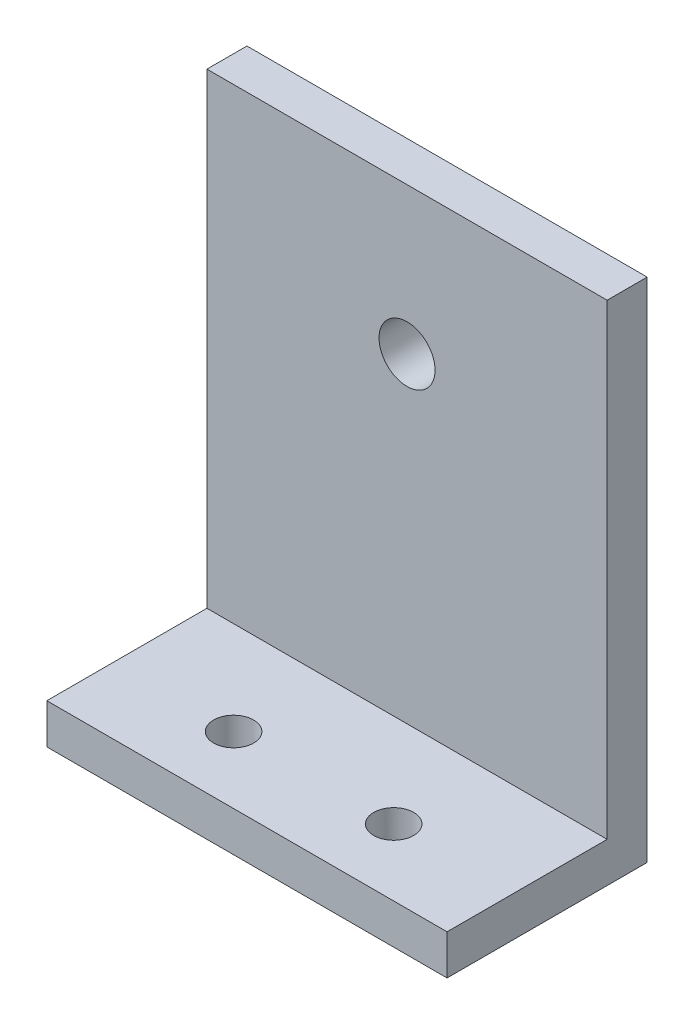
SolidWorks part; units mm, degrees
material "6063-O"
ref_plane "Front" through (0, 0, 0) normal (0, 0, 1) x (1, 0, 0)
ref_plane "Top" through (0, 0, 0) normal (0, 1, 0) x (1, 0, 0)
ref_plane "Right" through (0, 0, 0) normal (1, 0, 0) x (0, 0, -1)
sketch "草图1" plane through (0, 0, 0) normal (1, 0, 0) x (0, 0, -1)
  line L0 (0, 0) -> (0, 35)
  line L1 (0, 35) -> (3, 35)
  line L2 (3, 35) -> (3, -3)
  line L3 (0, 0) -> (-35, 0)
  line L4 (-35, 0) -> (-35, -3)
  line L5 (-35, -3) -> (3, -3)
  dimension "D1" = 35
  dimension "D2" = 3
  dimension "D3" = 38
  dimension "D4" = 35
extrude "凸台-拉伸1" add sketch "草图1" along normal blind 30
sketch "草图2" plane through (0, 0, 0) normal (0, 1, 0) x (1, 0, 0)
  line L0 (15, 0) -> (15, -35) construction
  line L1 (30, 0) -> (0, 0) construction
  line L2 (30, -35) -> (0, -35) construction
  line L3 (30, 3) -> (0, 3) construction
  line L4 (0, -35) -> (0, -25)
  line L5 (0, 0) -> (0, -35) construction
  line L6 (0, -25) -> (30, -25)
  line L7 (30, 0) -> (30, -35) construction
  line L8 (30, -25) -> (30, -35)
  line L9 (30, -35) -> (0, -35)
  circle A0 centre (9, -7) radius 1.5
  circle A1 centre (9, -19) radius 1.5
  circle A2 centre (21, -19) radius 1.5
  circle A3 centre (21, -7) radius 1.5
  dimension "D1" = 3
  dimension "D2" = 3
  dimension "D3" = 6
  dimension "D4" = 10
  dimension "D5" = 12
  dimension "D6" = 10
extrude "切除-拉伸1" cut sketch "草图2" against normal up to next
sketch "草图3" plane through (0, 0, 0) normal (0, 0, 1) x (1, 0, 0)
  line L0 (0, 35) -> (0, 0) construction
  line L1 (0, -3) -> (30, -3) construction
  circle A0 centre (15, 24) radius 2.1
  dimension "D1" = 4.2
  dimension "D2" = 15
  dimension "D3" = 27
extrude "切除-拉伸2" cut sketch "草图3" against normal through all
sketch "草图4" plane through (0, 0, 25) normal (0, 0, 1) x (1, 0, 0)
  line L4 (0, -3) -> (30, -3)
  line L5 (30, -3) -> (30, 0)
  line L6 (30, 0) -> (0, 0)
  line L7 (0, 0) -> (0, -3)
  line L8 (0, -3) -> (30, -3)
  line L9 (30, -3) -> (30, 0)
  line L10 (30, 0) -> (0, 0)
  line L11 (0, 0) -> (0, -3)
  dimension "D1" = 0
extrude "切除-拉伸3" cut sketch "草图4" against normal blind 13
sketch "草图5" plane through (0, 0, 0) normal (0, 0, 1) x (1, 0, 0)
  line L0 (0, 20) -> (15, 35)
  line L1 (0, 35) -> (0, 0) construction
  line L2 (30, 35) -> (0, 35) construction
  line L3 (15, 35) -> (30, 20)
  line L4 (30, 35) -> (30, 0) construction
  line L5 (30, 20) -> (30, 35)
  line L6 (30, 35) -> (0, 35)
  line L7 (0, 35) -> (0, 20)
  line L8 (7.5, 27.5) -> (22.5, 27.5)
  line M3 (0, 35) -> (0, 0)
  line M5 (30, 0) -> (30, 35)
  line M6 (30, 35) -> (0, 35)
  dimension "D1" = 15
extrude "切除-拉伸4" [suppressed] cut sketch "草图5" against normal through all and the other way through all contours L0 M3 M6 | L0 L8 L3 | L3 M6 M5
fillet "圆角1" [suppressed] radius 3
